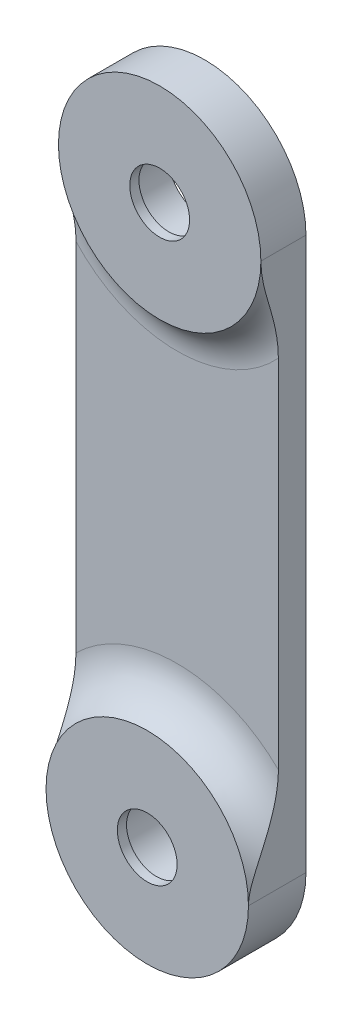
SolidWorks part; units mm, degrees
ref_plane "Plano frontal" through (0, 0, 0) normal (0, 0, 1) x (1, 0, 0)
ref_plane "Plano superior" through (0, 0, 0) normal (0, 1, 0) x (1, 0, 0)
ref_plane "Plano direito" through (0, 0, 0) normal (1, 0, 0) x (0, 0, -1)
sketch "Esboço1" plane through (0, 0, 0) normal (0, 0, 1) x (1, 0, 0)
  circle A3 centre (13.3842, -8.4275) radius 11 construction
  circle A5 centre (13.3842, -8.4275) radius 11
extrude "Ressalto-extrusão1" add sketch "Esboço1" against normal offset from surface (1.9 mm away) 2 offset beyond the face yes
sketch "Esboço3" plane through (0, 0, -1.9) normal (0, 0, -1) x (-1, 0, 0)
  line L0 (-24.3842, -8.4275) -> (-24.3842, -68.4275)
  line L1 (-2.3842, -8.4275) -> (-2.3842, -68.4275)
  arc A0 (-24.3842, -68.4275) -> (-2.3842, -68.4275) centre (-13.3842, -68.4275) ccw
  arc A7 (-2.3842, -8.4275) -> (-24.3842, -8.4275) centre (-13.3842, -8.4275) ccw
  circle A8 centre (-13.3842, -8.4275) radius 11 construction
  dimension "D1" = 60
extrude "Ressalto-extrusão3" add sketch "Esboço3" along normal blind 3
sketch "Esboço4" plane through (0, 0, -4.9) normal (0, 0, -1) x (-1, 0, 0)
  circle A0 centre (-13.3842, -8.4275) radius 3.25 construction
  circle A1 centre (-13.3842, -8.4275) radius 3.25
extrude "Corte-extrusão2" cut sketch "Esboço4" against normal through all
sketch "Esboço5" plane through (0, 0, -4.9) normal (0, 0, -1) x (-1, 0, 0)
  circle A0 centre (-13.3842, -8.4275) radius 4 construction
  circle A1 centre (-13.3842, -8.4275) radius 4
extrude "Corte-extrusão5" cut sketch "Esboço5" against normal offset from surface (3.9 mm away) 1 up to face at (10.1342, -8.4275, 0)
sketch "Esboço6" plane through (0, 0, -1.9) normal (0, 0, 1) x (1, 0, 0)
  circle A0 centre (13.3842, -68.4275) radius 11
  arc A1 (2.3842, -68.4275) -> (24.3842, -68.4275) centre (13.3842, -68.4275) ccw construction
extrude "Ressalto-extrusão4" add sketch "Esboço6" along normal offset from surface (3.25 mm away) 1 offset beyond the face yes
sketch "Esboço7" plane through (0, 0, -4.9) normal (0, 0, -1) x (-1, 0, 0)
  circle A0 centre (-13.3842, -68.4275) radius 4 construction
  circle A1 centre (-13.3842, -68.4275) radius 4
extrude "Corte-extrusão6" cut sketch "Esboço7" against normal offset from surface (5.25 mm away) 1 up to face at (13.3842, -79.4275, 1.35)
sketch "Esboço8" plane through (0, 0, -4.9) normal (0, 0, -1) x (-1, 0, 0)
  circle A0 centre (-13.3842, -68.4275) radius 3.25 construction
  circle A1 centre (-13.3842, -68.4275) radius 3.25
extrude "Corte-extrusão7" cut sketch "Esboço8" against normal through all
fillet "Filete1" radius 5 2 edges at (13.3842, -57.4275, -1.9) (13.3842, -19.4275, -1.9)
